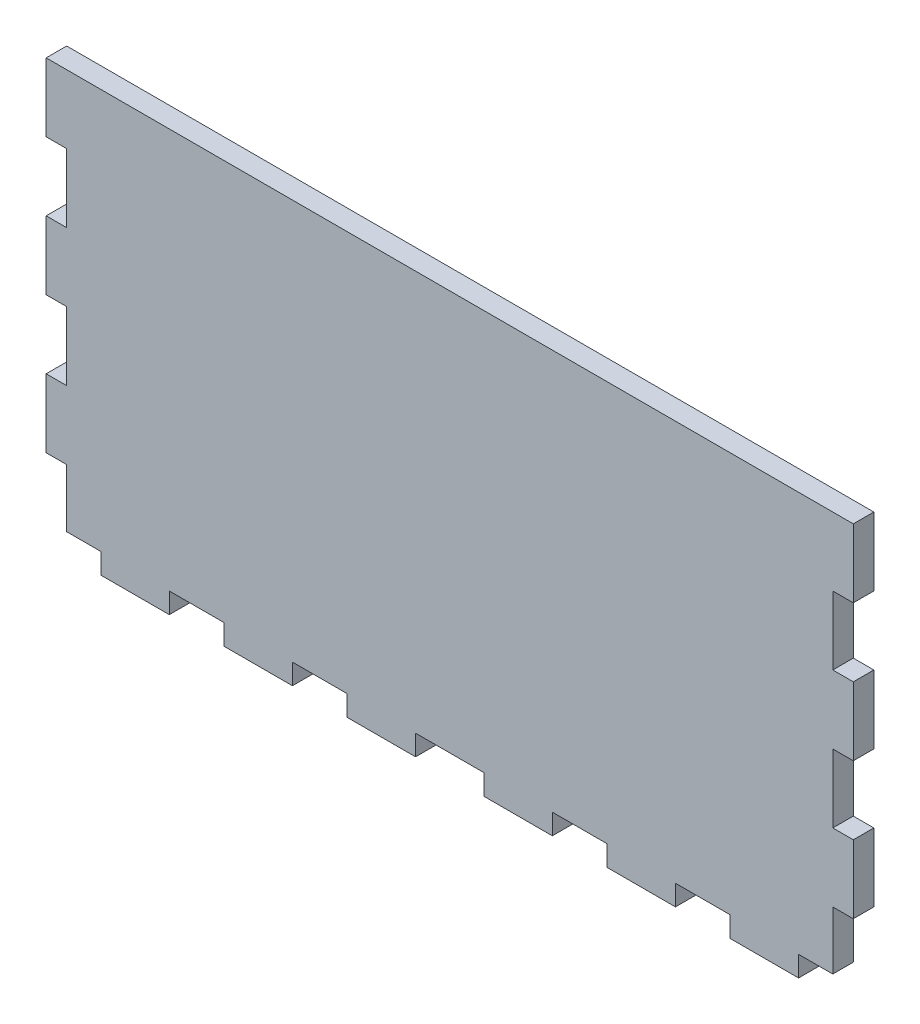
SolidWorks part; units mm, degrees
ref_plane "Front Plane" through (0, 0, 0) normal (0, 0, 1) x (1, 0, 0)
ref_plane "Top Plane" through (0, 0, 0) normal (0, 1, 0) x (1, 0, 0)
ref_plane "Right Plane" through (0, 0, 0) normal (1, 0, 0) x (0, 0, -1)
sketch "Sketch1" plane through (0, 0, 0) normal (0, 0, 1) x (1, 0, 0)
  line L0 (-56, 0) -> (56, 0) construction
  line L1 (0, -25.5) -> (0, 33) construction
  line L2 (-56, 33) -> (-59, 33)
  line L3 (-56, 33) -> (56, 33)
  line L4 (-59, 33) -> (-59, 23)
  line L5 (-23, -25.5) -> (-23, -28.5)
  line L6 (-59, 23) -> (-56, 23)
  line L7 (-56, 23) -> (-56, 13)
  line L8 (-56, 13) -> (-59, 13)
  line L9 (-59, 13) -> (-59, 3)
  line L10 (-59, 3) -> (-56, 3)
  line L11 (-56, 3) -> (-56, -7)
  line L12 (-56, -17) -> (-56, -25.5)
  line L13 (-56, -7) -> (-59, -7)
  line L14 (59, -7) -> (59, -17)
  line L15 (-56, -17) -> (-59, -17)
  line L16 (-59, -7) -> (-59, -17)
  line L17 (56, -17) -> (59, -17)
  line L18 (56, -7) -> (59, -7)
  line L19 (56, -17) -> (56, -25.5)
  line L20 (56, 3) -> (56, -7)
  line L21 (59, 3) -> (56, 3)
  line L22 (59, 13) -> (59, 3)
  line L23 (56, 13) -> (59, 13)
  line L24 (56, 23) -> (56, 13)
  line L25 (59, 23) -> (56, 23)
  line L26 (59, 33) -> (59, 23)
  line L27 (56, 33) -> (59, 33)
  line L28 (-5, -25.5) -> (5, -25.5)
  line L29 (-23, -28.5) -> (-33, -28.5)
  line L30 (-5, -25.5) -> (-5, -28.5)
  line L31 (-5, -28.5) -> (-15, -28.5)
  line L32 (-15, -25.5) -> (-15, -28.5)
  line L33 (-33, -25.5) -> (-33, -28.5)
  line L34 (-41, -25.5) -> (-41, -28.5)
  line L35 (-41, -28.5) -> (-51, -28.5)
  line L36 (-51, -25.5) -> (-51, -28.5)
  line L37 (-23, -25.5) -> (-15, -25.5)
  line L38 (-33, -25.5) -> (-41, -25.5)
  line L39 (-51, -25.5) -> (-56, -25.5)
  line L40 (51, -25.5) -> (56, -25.5)
  line L41 (33, -25.5) -> (41, -25.5)
  line L42 (23, -25.5) -> (15, -25.5)
  line L43 (51, -25.5) -> (51, -28.5)
  line L44 (41, -28.5) -> (51, -28.5)
  line L45 (41, -25.5) -> (41, -28.5)
  line L46 (33, -25.5) -> (33, -28.5)
  line L47 (15, -25.5) -> (15, -28.5)
  line L48 (5, -28.5) -> (15, -28.5)
  line L49 (5, -25.5) -> (5, -28.5)
  line L50 (23, -28.5) -> (33, -28.5)
  line L51 (23, -25.5) -> (23, -28.5)
  dimension "D1" = 112
  dimension "D2" = 25.5
  dimension "D3" = 5
  dimension "D4" = 58.5
  dimension "D5" = 3
  dimension "D6" = 112
  dimension "D8" = 10
  dimension "D9" = 3
  dimension "D10" = 3
  dimension "D11" = 3
  dimension "D7" = 10
  dimension "D13" = 2
  dimension "D12" = 10
  dimension "D14" = 10
  dimension "D15" = 3
extrude "Boss-Extrude1" add sketch "Sketch1" along normal blind 3
